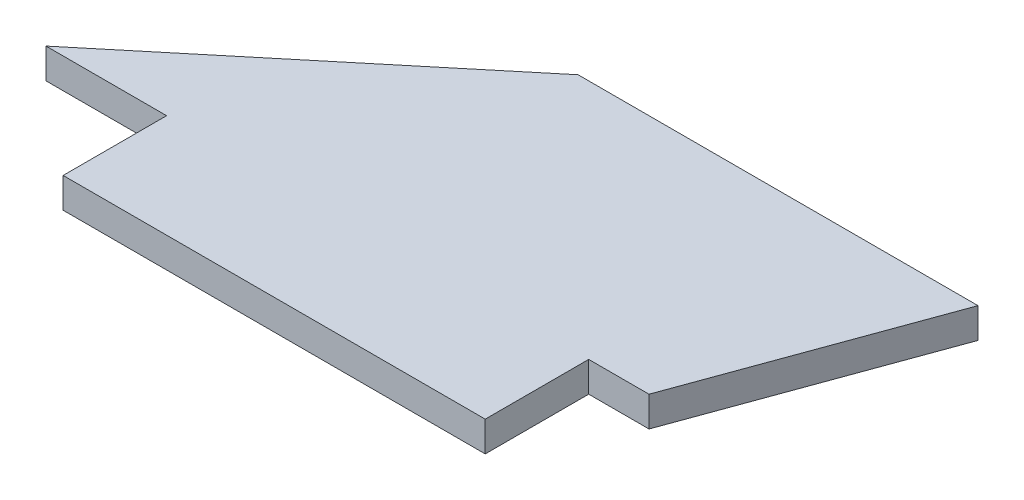
SolidWorks part; units mm, degrees
ref_plane "Front Plane" through (0, 0, 0) normal (0, 0, 1) x (1, 0, 0)
ref_plane "Top Plane" through (0, 0, 0) normal (0, 1, 0) x (1, 0, 0)
ref_plane "Right Plane" through (0, 0, 0) normal (1, 0, 0) x (0, 0, -1)
sketch "Sketch1" plane through (0, 0, 0) normal (0, 1, 0) x (1, 0, 0)
  line L0 (0, 0) -> (20, 0)
  line L1 (20, 0) -> (20, -17.16)
  line L2 (20, -17.16) -> (90, -17.16)
  line L3 (90, -17.16) -> (90, 0)
  line L4 (90, 0) -> (100, 0)
  line L5 (100, 0) -> (114.5588, 40)
  line L6 (114.5588, 40) -> (48.2388, 40)
  line L7 (48.2388, 40) -> (0, 0)
  point P5 (107.112, 40)
  dimension "D1" = 20
  dimension "D2" = 70
  dimension "D3" = 17.16
  dimension "D4" = 100
  dimension "D5" = 66.32
  dimension "D6" = 40
  dimension "D7" = 70
extrude "Boss-Extrude1" add sketch "Sketch1" along normal mid plane 5
